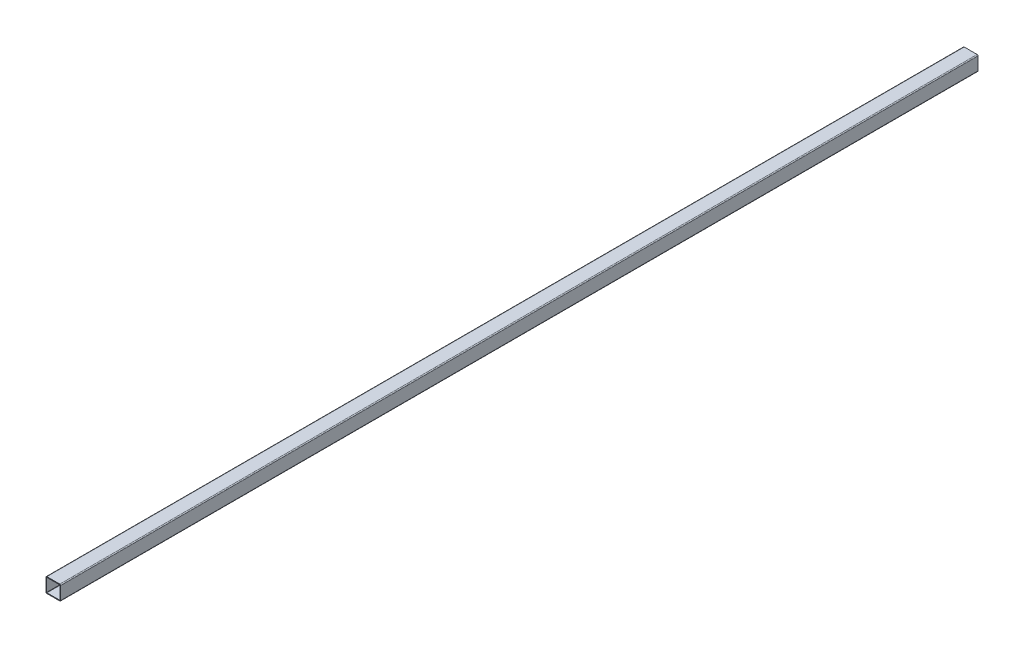
SolidWorks part; units mm, degrees
material "AISI 1010 Steel, hot rolled bar"
ref_plane "Front Plane" through (0, 0, 0) normal (0, 0, 1) x (1, 0, 0)
ref_plane "Top Plane" through (0, 0, 0) normal (0, 1, 0) x (1, 0, 0)
ref_plane "Right Plane" through (0, 0, 0) normal (1, 0, 0) x (0, 0, -1)
sketch "Sketch1" plane through (0, 0, 0) normal (0, 0, 1) x (1, 0, 0)
  line L0 (-14, 14.48) -> (14, 14.48)
  line L1 (-14, -16) -> (14, -16)
  line L2 (-16, -14) -> (-16, 14)
  line L3 (-14, 16) -> (14, 16)
  line L4 (16, -14) -> (16, 14)
  line L5 (-16, -16) -> (16, 16) construction
  line L6 (-16, 16) -> (16, -16) construction
  line L7 (14.48, -14) -> (14.48, 14)
  line L8 (-14, -14.48) -> (14, -14.48)
  line L9 (-14.48, -14) -> (-14.48, 14)
  arc A0 (14, -16) -> (16, -14) centre (14, -14) ccw
  arc A1 (-16, 14) -> (-14, 16) centre (-14, 14) cw
  arc A2 (-16, -14) -> (-14, -16) centre (-14, -14) ccw
  arc A3 (16, 14) -> (14, 16) centre (14, 14) ccw
  arc A4 (14.48, 14) -> (14, 14.48) centre (14, 14) ccw
  arc A5 (14, -14.48) -> (14.48, -14) centre (14, -14) ccw
  arc A6 (-14.48, -14) -> (-14, -14.48) centre (-14, -14) ccw
  arc A7 (-14.48, 14) -> (-14, 14.48) centre (-14, 14) cw
  point P0 (0, 0)
  dimension "D3" = 2
  dimension "D1" = 32
  dimension "D2" = 32
  dimension "D4" = 1.52
extrude "Boss-Extrude1" add sketch "Sketch1" along normal blind 1000 and the other way blind 1000
